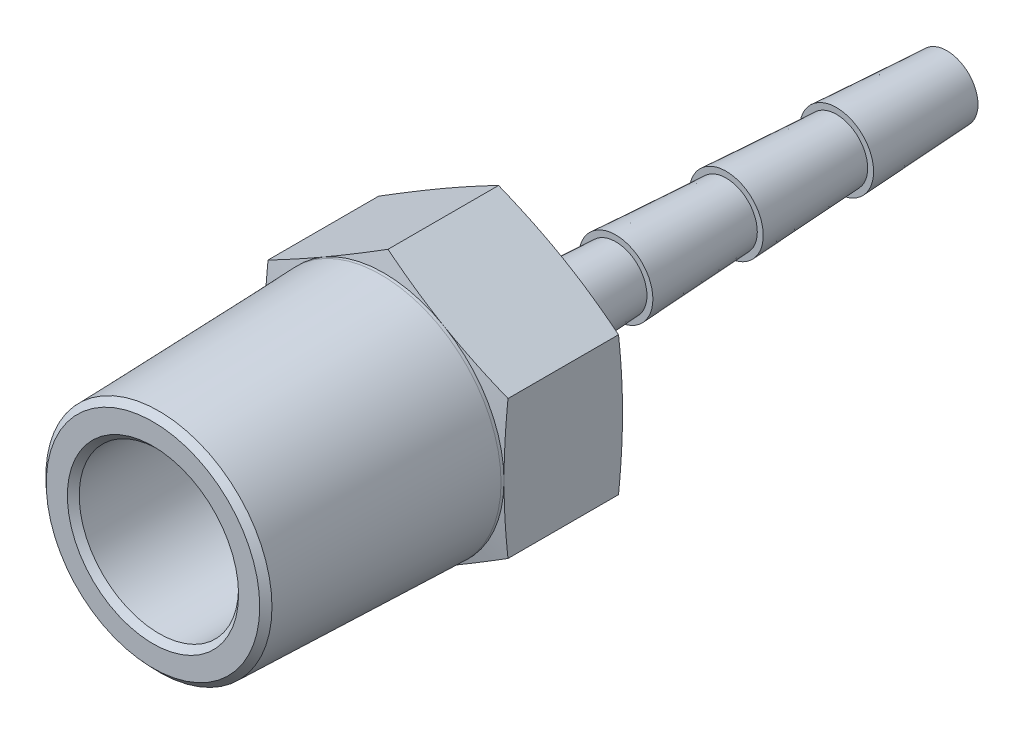
SolidWorks part; units mm, degrees
ref_plane "Front" through (0, 0, 0) normal (0, 0, 1) x (1, 0, 0)
ref_plane "Top" through (0, 0, 0) normal (0, 1, 0) x (1, 0, 0)
ref_plane "Right" through (0, 0, 0) normal (1, 0, 0) x (0, 0, -1)
sketch "PipeSketch" plane through (0, 0, 0) normal (0, 0, 1) x (1, 0, 0)
  circle A0 centre (0, 0) radius 5.1435
  circle A1 centre (0, 0) radius 1.0795
  dimension "OuterDiameter" = 10.287
  dimension "InnerDiameter" = 2.159
extrude "Extrusion" add sketch "PipeSketch" along normal blind 34.036
ref_plane "Plane5" through (0, 0, 19.05) normal (0, 0, -1) x (-1, 0, 0)
sketch "Sketch1" plane through (0, 0, 19.05) normal (0, 0, 1) x (1, 0, 0)
  line L1 (5.1435, 2.9696) -> (0, 5.9392)
  line L2 (0, 5.9392) -> (-5.1435, 2.9696)
  line L3 (-5.1435, 2.9696) -> (-5.1435, -2.9696)
  line L4 (-5.1435, -2.9696) -> (0, -5.9392)
  line L5 (0, -5.9392) -> (5.1435, -2.9696)
  line L6 (5.1435, -2.9696) -> (5.1435, 2.9696)
  circle A0 centre (0, 0) radius 5.1435 construction
  circle A1 centre (0, 0) radius 1.0795 construction
  circle A2 centre (0, 0) radius 1.0795
  dimension "D1" = 10.287
extrude "Boss-Extrude1" add sketch "Sketch1" along normal blind 5.08
sketch "FilterSketch" plane through (0, 0, 0) normal (0, 0, 1) x (1, 0, 0)
  circle A0 centre (0, 0) radius 1.5875
  dimension "NominalDiameter" = 3.175
sketch "Sketch9" plane through (0, 0, 34.036) normal (0, 0, 1) x (1, 0, 0)
  circle A0 centre (0, 0) radius 3.4163
  dimension "Thread end Dia" = 6.8326
extrude "Cut-Extrude1" cut sketch "Sketch9" against normal blind 9.906
sketch "Sketch7" plane through (0, 0, 0) normal (1, 0, 0) x (0, 0, -1)
  line L0 (-34.036, 5.1435) -> (-34.036, 4.8396)
  line L1 (-34.036, 5.1435) -> (-34.036, -5.1435) construction
  line L2 (-34.036, 4.8396) -> (-24.257, 5.1435)
  line L3 (-24.13, 5.1435) -> (-34.036, 5.1435) construction
  line L4 (-24.257, 5.1435) -> (-34.036, 5.1435)
  line L5 (0, 5.1435) -> (-19.05, 5.1435)
  line L6 (-19.05, 5.1435) -> (-19.05, 1.5875)
  line L7 (0, -5.1435) -> (0, 5.1435) construction
  line L8 (-19.05, 1.5875) -> (-18.923, 1.5875)
  line L9 (0, 0) -> (15.0254, 0) construction
  line L10 (-19.05, 2.9696) -> (-19.05, 4.4544) construction
  line L11 (-18.923, 1.5875) -> (-14.1922, 1.3335)
  line L12 (-14.1922, 1.3335) -> (-14.1922, 1.5875)
  line L13 (-14.1922, 1.5875) -> (-9.4615, 1.3335)
  line L14 (-9.4615, 1.3335) -> (-9.4615, 1.5875)
  line L15 (-9.4615, 1.5875) -> (-4.7307, 1.3335)
  line L16 (-4.7307, 1.3335) -> (-4.7307, 1.5875)
  line L17 (-4.7307, 1.5875) -> (0, 1.3335)
  line L19 (0, 1.3335) -> (0, 5.1435)
  dimension "D1" = 1.78
  dimension "Thread Length 1" = 9.779
  dimension "Hose dia" = 3.175
  dimension "D2" = 0.254
  dimension "Hose Length" = 18.923
  dimension "D3" = 4.7307
revolve "Cut-Revolve7" cut sketch "Sketch7" angle 360 about L9
sketch "Sketch4" plane through (0, 0, 0) normal (0, 1, 0) x (1, 0, 0)
  line L0 (-5.1435, -24.13) -> (-14.0335, -24.13)
  line L1 (-14.0335, -24.13) -> (-14.0335, -22.225)
  line L2 (-14.0335, -22.225) -> (-5.1435, -24.13)
  line L3 (-5.1435, -19.05) -> (-14.0335, -19.05)
  line L4 (-14.0335, -19.05) -> (-14.0335, -20.955)
  line L5 (-14.0335, -20.955) -> (-5.1435, -19.05)
  line L6 (0, 0) -> (0, -35.6608) construction
  dimension "D1" = 8.89
  dimension "D2" = 8.89
  dimension "D3" = 1.905
  dimension "D4" = 1.905
revolve "Cut-Revolve6" cut sketch "Sketch4" angle 360 about L6
chamfer "Chamfer1" distance 0.254 angle 45 2 edges at (4.8396, 0, 34.036) (3.4163, 0, 34.036) first distance on face at (5.1435, 0, 24.257) first distance on face at (3.4163, 0, 34.036)
ref_plane "Plane6" through (0, 0, 24.257) normal (0, 0, 1) x (1, 0, 0)
ref_plane "Plane7" through (0, 0, 21.59) normal (0, 0, -1) x (-1, 0, 0)
sketch "Sketch5" plane through (0, 0, 24.257) normal (0, 0, 1) x (1, 0, 0)
  point P0 (0, 0)
sketch "Sketch6" plane through (0, 0, 19.05) normal (0, 0, 1) x (1, 0, 0)
  point P0 (0, 0)
sketch "Sketch8" plane through (0, 0, 21.59) normal (0, 0, 1) x (1, 0, 0)
  point P0 (0, 0)
other "CPoint1" parameters "Diameter"=3.175, "StubLength"=38.1
ref_axis "Axis1" through (0, 0, 34.257) along (0, 0, -1)
other "CPoint2" parameters "Diameter"=3.175, "StubLength"=38.1
ref_axis "Axis2" through (0, 0, 9.05) along (0, 0, 1)
other "RPoint1"
equation "\"L\"= \"Length@Extrusion\""
equation "\"D1@Sketch1\"= \"OuterDiameter@PipeSketch\""
equation "\"L2\"= 0.39"
equation "\"D3@Sketch7\"=\"Hose Length@Sketch7\"/4"
equation "\"D1@Plane7\"= \"Hex Length@Boss-Extrude1\" / 2"
equation "\"D3@Sketch4\"=\"D4@Sketch4\""
equation "\"D2@Sketch4\"=\"D1@Sketch4\""
